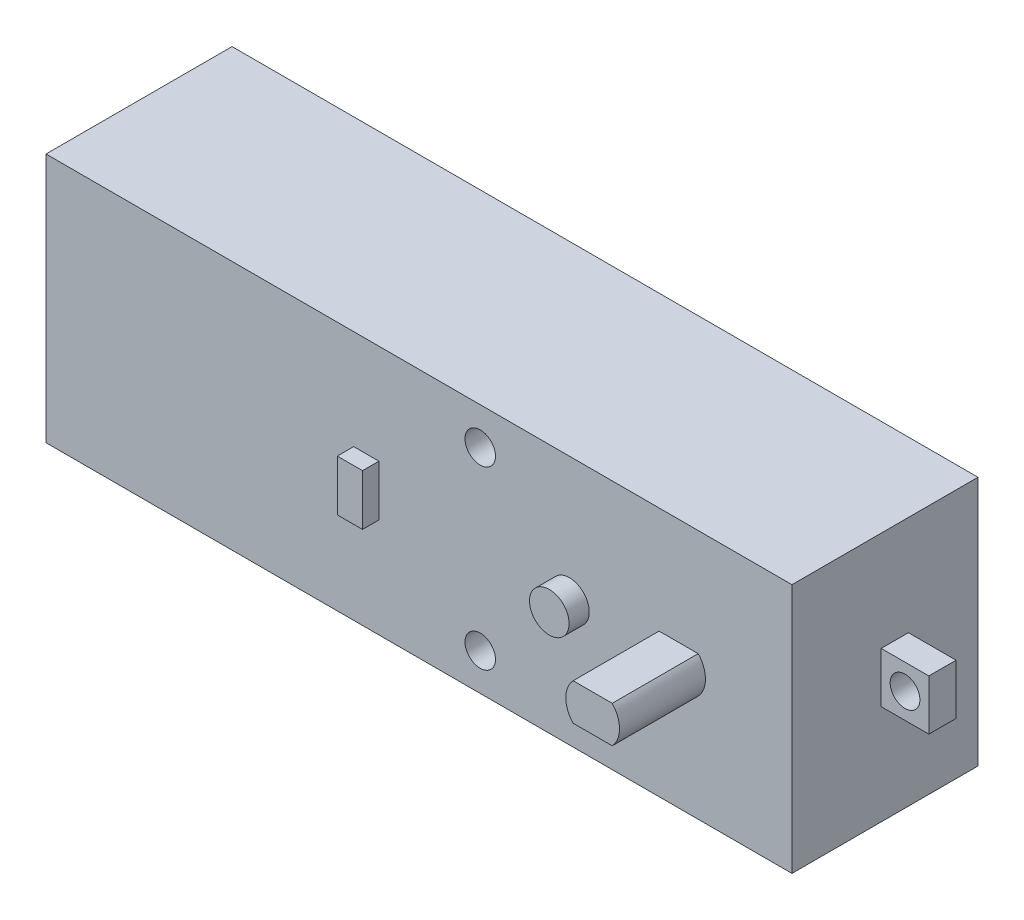
SolidWorks part; units mm, degrees
material "Copper"
ref_plane "Front Plane" through (0, 0, 0) normal (0, 0, 1) x (1, 0, 0)
ref_plane "Top Plane" through (0, 0, 0) normal (0, 1, 0) x (1, 0, 0)
ref_plane "Right Plane" through (0, 0, 0) normal (1, 0, 0) x (0, 0, -1)
sketch "Sketch1" plane through (0, 0, 0) normal (0, 0, 1) x (1, 0, 0)
  line L1 (0, 0) -> (75.1586, 0)
  line L2 (0, 0) -> (0, 25.1968)
  line L3 (0, 25.1968) -> (75.1586, 25.1968)
  line L4 (75.1586, 0) -> (75.1586, 25.1968)
  dimension "D1" = 75.1586
  dimension "D2" = 25.1968
extrude "Boss-Extrude1" add sketch "Sketch1" along normal blind 18.7452
ref_plane "Plane1" through (0, 0, 7.0104) normal (0, 0, 1) x (1, 0, 0)
sketch "Sketch2" plane through (0, 0, 7.0104) normal (0, 0, 1) x (1, 0, 0)
  line L0 (75.1586, 0) -> (75.1586, 25.1968) construction
  line L1 (75.1586, 10.0584) -> (79.9592, 10.0584)
  line L2 (75.1586, 10.0584) -> (75.1586, 15.1384)
  line L3 (75.1586, 15.1384) -> (79.9592, 15.1384)
  line L4 (79.9592, 10.0584) -> (79.9592, 15.1384)
  point P6 (75.1586, 12.5984)
  point P7 (75.1586, 12.5984)
  dimension "D1" = 5.08
  dimension "D2" = 4.8006
extrude "Boss-Extrude2" add sketch "Sketch2" along normal blind 2.7432
sketch "Sketch4" plane through (0, 0, 9.7536) normal (0, 0, 1) x (1, 0, 0)
  line L0 (75.1586, 15.1384) -> (79.9592, 10.0584) construction
  circle A0 centre (77.5589, 12.5984) radius 1.4986
  dimension "D1" = 2.9972
extrude "Cut-Extrude1" cut sketch "Sketch4" against normal through all
sketch "Sketch3" plane through (0, 0, 18.7452) normal (0, 0, 1) x (1, 0, 0)
  line L0 (0, 25.1968) -> (0, 0) construction
  circle A0 centre (52.7431, 12.5984) radius 1.9939
  circle A1 centre (77.5589, 12.5984) radius 1.4986 construction
  point P4 (0, 12.5984)
  dimension "D1" = 3.9878
  dimension "D2" = 24.8158
extrude "Boss-Extrude3" add sketch "Sketch3" along normal blind 2.032
sketch "Sketch5" plane through (0, 0, 18.7452) normal (0, 0, 1) x (1, 0, 0)
  line L0 (0, 25.1968) -> (0, 0) construction
  circle A0 centre (63.7413, 12.5984) radius 2.7051
  circle A2 centre (52.7431, 12.5984) radius 1.9939 construction
  point P7 (0, 12.5984)
  dimension "D1" = 5.4102
  dimension "D2" = 10.9982
extrude "Boss-Extrude4" add sketch "Sketch5" along normal blind 8.6614
sketch "Sketch6" plane through (0, 0, 27.4066) normal (0, 0, 1) x (1, 0, 0)
  line L0 (61.7717, 10.7442) -> (65.7109, 10.7442)
  line L1 (61.7717, 14.4526) -> (65.7109, 14.4526)
  circle A0 centre (63.7413, 12.5984) radius 2.7051 construction
  circle A1 centre (63.7413, 12.5984) radius 2.7051
  circle M3 centre (63.7413, 12.5984) radius 2.7051
  dimension "D1" = 3.7084
extrude "Cut-Extrude2" cut sketch "Sketch6" against normal up to surface (8.6614 mm away) contours L1 M3 | L0 M3 region at (63.7413, 10.3988, 27.4066) region at (63.7413, 14.798, 27.4066) up to face at (61.0362, 12.5984, 18.7452)
sketch "Sketch7" plane through (0, 0, 18.7452) normal (0, 0, 1) x (1, 0, 0)
  line L0 (43.7515, 21.463) -> (43.7515, 3.7338) construction
  line L1 (43.7515, 12.5984) -> (0, 12.5984) construction
  line L2 (0, 25.1968) -> (0, 0) construction
  circle A0 centre (43.7515, 21.463) radius 1.5367
  circle A1 centre (43.7515, 3.7338) radius 1.5367
  circle A2 centre (52.7431, 12.5984) radius 1.9939 construction
  dimension "D1" = 3.0734
  dimension "D2" = 8.9916
  dimension "D3" = 17.7292
extrude "Cut-Extrude3" cut sketch "Sketch7" against normal through all
sketch "Sketch8" plane through (0, 0, 18.7452) normal (0, 0, 1) x (1, 0, 0)
  line L0 (33.5407, 12.5984) -> (52.7431, 12.5984) construction
  line L1 (31.0007, 15.1638) -> (33.5407, 15.1638)
  line L2 (31.0007, 15.1638) -> (31.0007, 10.033)
  line L3 (31.0007, 10.033) -> (33.5407, 10.033)
  line L4 (33.5407, 15.1638) -> (33.5407, 10.033)
  dimension "D1" = 5.1308
  dimension "D2" = 2.54
  dimension "D3" = 19.2024
extrude "Boss-Extrude5" add sketch "Sketch8" along normal blind 1.651
ref_plane "Plane2" through (0, 12.5984, 0) normal (0, 1, 0) x (1, 0, 0)
